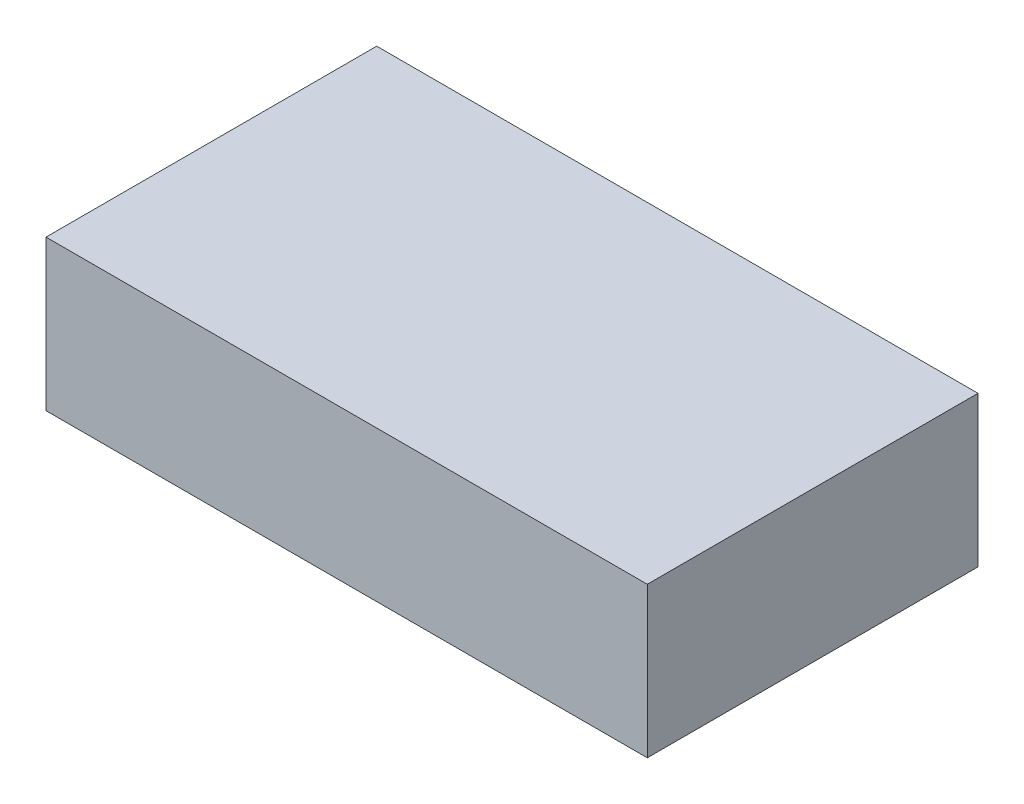
SolidWorks part; units mm, degrees
ref_plane "Front Plane" through (0, 0, 0) normal (0, 0, 1) x (1, 0, 0)
ref_plane "Top Plane" through (0, 0, 0) normal (0, 1, 0) x (1, 0, 0)
ref_plane "Right Plane" through (0, 0, 0) normal (1, 0, 0) x (0, 0, -1)
sketch "Sketch1" plane through (0, 0, 0) normal (0, 1, 0) x (1, 0, 0)
  line L1 (0, 0) -> (200, 0)
  line L2 (0, 0) -> (0, 110)
  line L3 (0, 110) -> (200, 110)
  line L4 (200, 0) -> (200, 110)
  dimension "D1" = 200
  dimension "D2" = 110
extrude "Boss-Extrude1" add sketch "Sketch1" along normal blind 50
